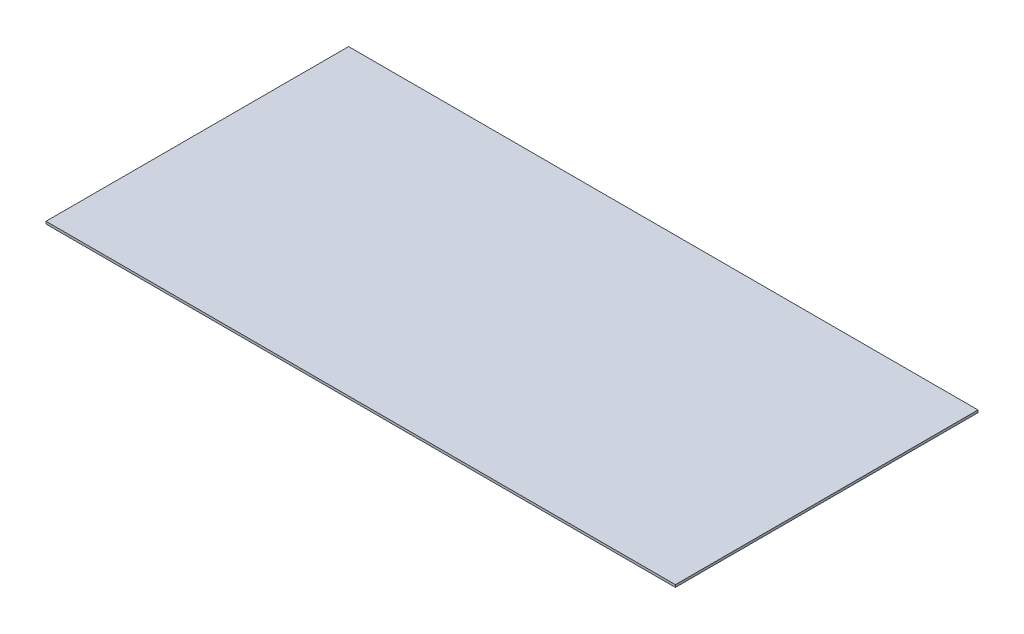
SolidWorks part; units mm, degrees
ref_plane "Front Plane" through (0, 0, 0) normal (0, 0, 1) x (1, 0, 0)
ref_plane "Top Plane" through (0, 0, 0) normal (0, 1, 0) x (1, 0, 0)
ref_plane "Right Plane" through (0, 0, 0) normal (1, 0, 0) x (0, 0, -1)
sketch "Sketch2" plane through (0, 0, 0) normal (0, 1, 0) x (1, 0, 0)
  line L1 (0, 1250) -> (2600, 1250)
  line L2 (0, 1250) -> (0, 0)
  line L3 (0, 0) -> (2600, 0)
  line L4 (2600, 1250) -> (2600, 0)
  dimension "Width" = 1250
  dimension "Length" = 2600
extrude "Extrude1" add sketch "Sketch2" along normal blind 10
sheet metal parameters "Sheet-Metal1" thickness 10 parameters "D1"=10
convert to sheet metal "Convert-Solid1" parameters "D1"=10
sketch "Etch" plane through (0, 0, 0) normal (0, -1, 0) x (1, 0, 0)
  line L0 (2572, -160) -> (2422, -160) construction
  line L1 (2572, -90) -> (2422, -90) construction
  line L2 (2572, -90) -> (2572, -120) construction
  line L3 (2572, -160) -> (2572, -190) construction
  line L4 (2572, -190) -> (2422, -190) construction
  line L5 (2422, -160) -> (2422, -190) construction
  line L6 (2572, -120) -> (2422, -120) construction
  line L7 (2422, -90) -> (2422, -120) construction
  line L8 (2422, -1130) -> (2422, -1160) construction
  line L9 (2572, -1160) -> (2422, -1160) construction
  line L10 (2572, -1130) -> (2572, -1160) construction
  line L11 (2572, -1130) -> (2422, -1130) construction
  line L12 (2572, -1060) -> (2572, -1090) construction
  line L13 (2572, -1060) -> (2422, -1060) construction
  line L14 (2422, -1060) -> (2422, -1090) construction
  line L15 (2572, -1090) -> (2422, -1090) construction
  line L16 (2572, -160) -> (2422, -160)
  line L17 (2572, -90) -> (2422, -90)
  line L18 (2572, -90) -> (2572, -120)
  line L19 (2572, -160) -> (2572, -190)
  line L20 (2572, -190) -> (2422, -190)
  line L21 (2422, -160) -> (2422, -190)
  line L22 (2572, -120) -> (2422, -120)
  line L23 (2422, -90) -> (2422, -120)
  line L24 (2422, -1130) -> (2422, -1160)
  line L25 (2572, -1160) -> (2422, -1160)
  line L26 (2572, -1130) -> (2572, -1160)
  line L27 (2572, -1130) -> (2422, -1130)
  line L28 (2572, -1060) -> (2572, -1090)
  line L29 (2572, -1060) -> (2422, -1060)
  line L30 (2422, -1060) -> (2422, -1090)
  line L31 (2572, -1090) -> (2422, -1090)
sketch "Sketch4" plane through (0, 10, 0) normal (0, 1, 0) x (1, 0, 0)
  circle A0 centre (1184.0011, 660.7352) radius 330.6526
sketch "Sketch5" plane through (0, 10, 0) normal (0, 1, 0) x (1, 0, 0)
  circle A0 centre (1179.6151, 596.7354) radius 277.3059
flat pattern "Flat-Pattern1" [suppressed]
sketch "Bend-Lines1" plane through (0, 0, 0) normal (0, 1, 0) x (1, 0, 0)
sketch3d "Bounding-Box1" [suppressed]
  line L0 (2600, 0, 0) -> (0, 0, 0) construction
  line L1 (2600, 1250, 0) -> (0, 1250, 0) construction
  line L2 (2600, 0, 0) -> (2600, 1250, 0) construction
  line L3 (0, 0, 0) -> (0, 1250, 0) construction
sketch "Etch-1" plane through (0, 0, 0) normal (0, -1, 0) x (1, 0, 0)
  line L16 (2572, -160) -> (2422, -160)
  line L17 (2572, -90) -> (2422, -90)
  line L18 (2572, -90) -> (2572, -120)
  line L19 (2572, -160) -> (2572, -190)
  line L20 (2572, -190) -> (2422, -190)
  line L21 (2422, -160) -> (2422, -190)
  line L22 (2572, -120) -> (2422, -120)
  line L23 (2422, -90) -> (2422, -120)
  line L24 (2422, -1130) -> (2422, -1160)
  line L25 (2572, -1160) -> (2422, -1160)
  line L26 (2572, -1130) -> (2572, -1160)
  line L27 (2572, -1130) -> (2422, -1130)
  line L28 (2572, -1060) -> (2572, -1090)
  line L29 (2572, -1060) -> (2422, -1060)
  line L30 (2422, -1060) -> (2422, -1090)
  line L31 (2572, -1090) -> (2422, -1090)
sketch "Etch-2" plane through (0, 0, 0) normal (0, -1, 0) x (1, 0, 0)
  line L16 (2572, -160) -> (2422, -160)
  line L17 (2572, -90) -> (2422, -90)
  line L18 (2572, -90) -> (2572, -120)
  line L19 (2572, -160) -> (2572, -190)
  line L20 (2572, -190) -> (2422, -190)
  line L21 (2422, -160) -> (2422, -190)
  line L22 (2572, -120) -> (2422, -120)
  line L23 (2422, -90) -> (2422, -120)
  line L24 (2422, -1130) -> (2422, -1160)
  line L25 (2572, -1160) -> (2422, -1160)
  line L26 (2572, -1130) -> (2572, -1160)
  line L27 (2572, -1130) -> (2422, -1130)
  line L28 (2572, -1060) -> (2572, -1090)
  line L29 (2572, -1060) -> (2422, -1060)
  line L30 (2422, -1060) -> (2422, -1090)
  line L31 (2572, -1090) -> (2422, -1090)
sketch "Etch-3" plane through (0, 0, 0) normal (0, -1, 0) x (1, 0, 0)
  line L16 (2572, -160) -> (2422, -160)
  line L17 (2572, -90) -> (2422, -90)
  line L18 (2572, -90) -> (2572, -120)
  line L19 (2572, -160) -> (2572, -190)
  line L20 (2572, -190) -> (2422, -190)
  line L21 (2422, -160) -> (2422, -190)
  line L22 (2572, -120) -> (2422, -120)
  line L23 (2422, -90) -> (2422, -120)
  line L24 (2422, -1130) -> (2422, -1160)
  line L25 (2572, -1160) -> (2422, -1160)
  line L26 (2572, -1130) -> (2572, -1160)
  line L27 (2572, -1130) -> (2422, -1130)
  line L28 (2572, -1060) -> (2572, -1090)
  line L29 (2572, -1060) -> (2422, -1060)
  line L30 (2422, -1060) -> (2422, -1090)
  line L31 (2572, -1090) -> (2422, -1090)
sketch "Etch-4" plane through (0, 0, 0) normal (0, -1, 0) x (1, 0, 0)
  line L16 (2572, -160) -> (2422, -160)
  line L17 (2572, -90) -> (2422, -90)
  line L18 (2572, -90) -> (2572, -120)
  line L19 (2572, -160) -> (2572, -190)
  line L20 (2572, -190) -> (2422, -190)
  line L21 (2422, -160) -> (2422, -190)
  line L22 (2572, -120) -> (2422, -120)
  line L23 (2422, -90) -> (2422, -120)
  line L24 (2422, -1130) -> (2422, -1160)
  line L25 (2572, -1160) -> (2422, -1160)
  line L26 (2572, -1130) -> (2572, -1160)
  line L27 (2572, -1130) -> (2422, -1130)
  line L28 (2572, -1060) -> (2572, -1090)
  line L29 (2572, -1060) -> (2422, -1060)
  line L30 (2422, -1060) -> (2422, -1090)
  line L31 (2572, -1090) -> (2422, -1090)
sketch "Etch-5" plane through (0, 0, 0) normal (0, -1, 0) x (1, 0, 0)
  line L16 (2572, -160) -> (2422, -160)
  line L17 (2572, -90) -> (2422, -90)
  line L18 (2572, -90) -> (2572, -120)
  line L19 (2572, -160) -> (2572, -190)
  line L20 (2572, -190) -> (2422, -190)
  line L21 (2422, -160) -> (2422, -190)
  line L22 (2572, -120) -> (2422, -120)
  line L23 (2422, -90) -> (2422, -120)
  line L24 (2422, -1130) -> (2422, -1160)
  line L25 (2572, -1160) -> (2422, -1160)
  line L26 (2572, -1130) -> (2572, -1160)
  line L27 (2572, -1130) -> (2422, -1130)
  line L28 (2572, -1060) -> (2572, -1090)
  line L29 (2572, -1060) -> (2422, -1060)
  line L30 (2422, -1060) -> (2422, -1090)
  line L31 (2572, -1090) -> (2422, -1090)
sketch "Etch-6" plane through (0, 0, 0) normal (0, -1, 0) x (1, 0, 0)
  line L16 (2572, -160) -> (2422, -160)
  line L17 (2572, -90) -> (2422, -90)
  line L18 (2572, -90) -> (2572, -120)
  line L19 (2572, -160) -> (2572, -190)
  line L20 (2572, -190) -> (2422, -190)
  line L21 (2422, -160) -> (2422, -190)
  line L22 (2572, -120) -> (2422, -120)
  line L23 (2422, -90) -> (2422, -120)
  line L24 (2422, -1130) -> (2422, -1160)
  line L25 (2572, -1160) -> (2422, -1160)
  line L26 (2572, -1130) -> (2572, -1160)
  line L27 (2572, -1130) -> (2422, -1130)
  line L28 (2572, -1060) -> (2572, -1090)
  line L29 (2572, -1060) -> (2422, -1060)
  line L30 (2422, -1060) -> (2422, -1090)
  line L31 (2572, -1090) -> (2422, -1090)
sketch "Etch-7" plane through (0, 0, 0) normal (0, -1, 0) x (1, 0, 0)
  line L16 (2572, -160) -> (2422, -160)
  line L17 (2572, -90) -> (2422, -90)
  line L18 (2572, -90) -> (2572, -120)
  line L19 (2572, -160) -> (2572, -190)
  line L20 (2572, -190) -> (2422, -190)
  line L21 (2422, -160) -> (2422, -190)
  line L22 (2572, -120) -> (2422, -120)
  line L23 (2422, -90) -> (2422, -120)
  line L24 (2422, -1130) -> (2422, -1160)
  line L25 (2572, -1160) -> (2422, -1160)
  line L26 (2572, -1130) -> (2572, -1160)
  line L27 (2572, -1130) -> (2422, -1130)
  line L28 (2572, -1060) -> (2572, -1090)
  line L29 (2572, -1060) -> (2422, -1060)
  line L30 (2422, -1060) -> (2422, -1090)
  line L31 (2572, -1090) -> (2422, -1090)
sketch "Etch-8" plane through (0, 0, 0) normal (0, -1, 0) x (1, 0, 0)
  line L16 (2572, -160) -> (2422, -160)
  line L17 (2572, -90) -> (2422, -90)
  line L18 (2572, -90) -> (2572, -120)
  line L19 (2572, -160) -> (2572, -190)
  line L20 (2572, -190) -> (2422, -190)
  line L21 (2422, -160) -> (2422, -190)
  line L22 (2572, -120) -> (2422, -120)
  line L23 (2422, -90) -> (2422, -120)
  line L24 (2422, -1130) -> (2422, -1160)
  line L25 (2572, -1160) -> (2422, -1160)
  line L26 (2572, -1130) -> (2572, -1160)
  line L27 (2572, -1130) -> (2422, -1130)
  line L28 (2572, -1060) -> (2572, -1090)
  line L29 (2572, -1060) -> (2422, -1060)
  line L30 (2422, -1060) -> (2422, -1090)
  line L31 (2572, -1090) -> (2422, -1090)
sketch "Etch-9" plane through (0, 0, 0) normal (0, -1, 0) x (1, 0, 0)
  line L16 (2572, -160) -> (2422, -160)
  line L17 (2572, -90) -> (2422, -90)
  line L18 (2572, -90) -> (2572, -120)
  line L19 (2572, -160) -> (2572, -190)
  line L20 (2572, -190) -> (2422, -190)
  line L21 (2422, -160) -> (2422, -190)
  line L22 (2572, -120) -> (2422, -120)
  line L23 (2422, -90) -> (2422, -120)
  line L24 (2422, -1130) -> (2422, -1160)
  line L25 (2572, -1160) -> (2422, -1160)
  line L26 (2572, -1130) -> (2572, -1160)
  line L27 (2572, -1130) -> (2422, -1130)
  line L28 (2572, -1060) -> (2572, -1090)
  line L29 (2572, -1060) -> (2422, -1060)
  line L30 (2422, -1060) -> (2422, -1090)
  line L31 (2572, -1090) -> (2422, -1090)
sketch "Etch-10" plane through (0, 0, 0) normal (0, -1, 0) x (1, 0, 0)
  line L16 (2572, -160) -> (2422, -160)
  line L17 (2572, -90) -> (2422, -90)
  line L18 (2572, -90) -> (2572, -120)
  line L19 (2572, -160) -> (2572, -190)
  line L20 (2572, -190) -> (2422, -190)
  line L21 (2422, -160) -> (2422, -190)
  line L22 (2572, -120) -> (2422, -120)
  line L23 (2422, -90) -> (2422, -120)
  line L24 (2422, -1130) -> (2422, -1160)
  line L25 (2572, -1160) -> (2422, -1160)
  line L26 (2572, -1130) -> (2572, -1160)
  line L27 (2572, -1130) -> (2422, -1130)
  line L28 (2572, -1060) -> (2572, -1090)
  line L29 (2572, -1060) -> (2422, -1060)
  line L30 (2422, -1060) -> (2422, -1090)
  line L31 (2572, -1090) -> (2422, -1090)
sketch "Etch-11" plane through (0, 0, 0) normal (0, -1, 0) x (1, 0, 0)
  line L16 (2572, -160) -> (2422, -160)
  line L17 (2572, -90) -> (2422, -90)
  line L18 (2572, -90) -> (2572, -120)
  line L19 (2572, -160) -> (2572, -190)
  line L20 (2572, -190) -> (2422, -190)
  line L21 (2422, -160) -> (2422, -190)
  line L22 (2572, -120) -> (2422, -120)
  line L23 (2422, -90) -> (2422, -120)
  line L24 (2422, -1130) -> (2422, -1160)
  line L25 (2572, -1160) -> (2422, -1160)
  line L26 (2572, -1130) -> (2572, -1160)
  line L27 (2572, -1130) -> (2422, -1130)
  line L28 (2572, -1060) -> (2572, -1090)
  line L29 (2572, -1060) -> (2422, -1060)
  line L30 (2422, -1060) -> (2422, -1090)
  line L31 (2572, -1090) -> (2422, -1090)
sketch "Etch-12" plane through (0, 0, 0) normal (0, -1, 0) x (1, 0, 0)
  line L16 (2572, -160) -> (2422, -160)
  line L17 (2572, -90) -> (2422, -90)
  line L18 (2572, -90) -> (2572, -120)
  line L19 (2572, -160) -> (2572, -190)
  line L20 (2572, -190) -> (2422, -190)
  line L21 (2422, -160) -> (2422, -190)
  line L22 (2572, -120) -> (2422, -120)
  line L23 (2422, -90) -> (2422, -120)
  line L24 (2422, -1130) -> (2422, -1160)
  line L25 (2572, -1160) -> (2422, -1160)
  line L26 (2572, -1130) -> (2572, -1160)
  line L27 (2572, -1130) -> (2422, -1130)
  line L28 (2572, -1060) -> (2572, -1090)
  line L29 (2572, -1060) -> (2422, -1060)
  line L30 (2422, -1060) -> (2422, -1090)
  line L31 (2572, -1090) -> (2422, -1090)
sketch "Etch-13" plane through (0, 0, 0) normal (0, -1, 0) x (1, 0, 0)
  line L16 (2572, -160) -> (2422, -160)
  line L17 (2572, -90) -> (2422, -90)
  line L18 (2572, -90) -> (2572, -120)
  line L19 (2572, -160) -> (2572, -190)
  line L20 (2572, -190) -> (2422, -190)
  line L21 (2422, -160) -> (2422, -190)
  line L22 (2572, -120) -> (2422, -120)
  line L23 (2422, -90) -> (2422, -120)
  line L24 (2422, -1130) -> (2422, -1160)
  line L25 (2572, -1160) -> (2422, -1160)
  line L26 (2572, -1130) -> (2572, -1160)
  line L27 (2572, -1130) -> (2422, -1130)
  line L28 (2572, -1060) -> (2572, -1090)
  line L29 (2572, -1060) -> (2422, -1060)
  line L30 (2422, -1060) -> (2422, -1090)
  line L31 (2572, -1090) -> (2422, -1090)
sketch "Etch-14" plane through (0, 0, 0) normal (0, -1, 0) x (1, 0, 0)
  line L16 (2572, -160) -> (2422, -160)
  line L17 (2572, -90) -> (2422, -90)
  line L18 (2572, -90) -> (2572, -120)
  line L19 (2572, -160) -> (2572, -190)
  line L20 (2572, -190) -> (2422, -190)
  line L21 (2422, -160) -> (2422, -190)
  line L22 (2572, -120) -> (2422, -120)
  line L23 (2422, -90) -> (2422, -120)
  line L24 (2422, -1130) -> (2422, -1160)
  line L25 (2572, -1160) -> (2422, -1160)
  line L26 (2572, -1130) -> (2572, -1160)
  line L27 (2572, -1130) -> (2422, -1130)
  line L28 (2572, -1060) -> (2572, -1090)
  line L29 (2572, -1060) -> (2422, -1060)
  line L30 (2422, -1060) -> (2422, -1090)
  line L31 (2572, -1090) -> (2422, -1090)
sketch "Etch-15" plane through (0, 0, 0) normal (0, -1, 0) x (1, 0, 0)
  line L16 (2572, -160) -> (2422, -160)
  line L17 (2572, -90) -> (2422, -90)
  line L18 (2572, -90) -> (2572, -120)
  line L19 (2572, -160) -> (2572, -190)
  line L20 (2572, -190) -> (2422, -190)
  line L21 (2422, -160) -> (2422, -190)
  line L22 (2572, -120) -> (2422, -120)
  line L23 (2422, -90) -> (2422, -120)
  line L24 (2422, -1130) -> (2422, -1160)
  line L25 (2572, -1160) -> (2422, -1160)
  line L26 (2572, -1130) -> (2572, -1160)
  line L27 (2572, -1130) -> (2422, -1130)
  line L28 (2572, -1060) -> (2572, -1090)
  line L29 (2572, -1060) -> (2422, -1060)
  line L30 (2422, -1060) -> (2422, -1090)
  line L31 (2572, -1090) -> (2422, -1090)
sketch "Etch-16" plane through (0, 0, 0) normal (0, -1, 0) x (1, 0, 0)
  line L16 (2572, -160) -> (2422, -160)
  line L17 (2572, -90) -> (2422, -90)
  line L18 (2572, -90) -> (2572, -120)
  line L19 (2572, -160) -> (2572, -190)
  line L20 (2572, -190) -> (2422, -190)
  line L21 (2422, -160) -> (2422, -190)
  line L22 (2572, -120) -> (2422, -120)
  line L23 (2422, -90) -> (2422, -120)
  line L24 (2422, -1130) -> (2422, -1160)
  line L25 (2572, -1160) -> (2422, -1160)
  line L26 (2572, -1130) -> (2572, -1160)
  line L27 (2572, -1130) -> (2422, -1130)
  line L28 (2572, -1060) -> (2572, -1090)
  line L29 (2572, -1060) -> (2422, -1060)
  line L30 (2422, -1060) -> (2422, -1090)
  line L31 (2572, -1090) -> (2422, -1090)
sketch "Etch-17" plane through (0, 0, 0) normal (0, -1, 0) x (1, 0, 0)
  line L16 (2572, -160) -> (2422, -160)
  line L17 (2572, -90) -> (2422, -90)
  line L18 (2572, -90) -> (2572, -120)
  line L19 (2572, -160) -> (2572, -190)
  line L20 (2572, -190) -> (2422, -190)
  line L21 (2422, -160) -> (2422, -190)
  line L22 (2572, -120) -> (2422, -120)
  line L23 (2422, -90) -> (2422, -120)
  line L24 (2422, -1130) -> (2422, -1160)
  line L25 (2572, -1160) -> (2422, -1160)
  line L26 (2572, -1130) -> (2572, -1160)
  line L27 (2572, -1130) -> (2422, -1130)
  line L28 (2572, -1060) -> (2572, -1090)
  line L29 (2572, -1060) -> (2422, -1060)
  line L30 (2422, -1060) -> (2422, -1090)
  line L31 (2572, -1090) -> (2422, -1090)
sketch "Etch-18" plane through (0, 0, 0) normal (0, -1, 0) x (1, 0, 0)
  line L16 (2572, -160) -> (2422, -160)
  line L17 (2572, -90) -> (2422, -90)
  line L18 (2572, -90) -> (2572, -120)
  line L19 (2572, -160) -> (2572, -190)
  line L20 (2572, -190) -> (2422, -190)
  line L21 (2422, -160) -> (2422, -190)
  line L22 (2572, -120) -> (2422, -120)
  line L23 (2422, -90) -> (2422, -120)
  line L24 (2422, -1130) -> (2422, -1160)
  line L25 (2572, -1160) -> (2422, -1160)
  line L26 (2572, -1130) -> (2572, -1160)
  line L27 (2572, -1130) -> (2422, -1130)
  line L28 (2572, -1060) -> (2572, -1090)
  line L29 (2572, -1060) -> (2422, -1060)
  line L30 (2422, -1060) -> (2422, -1090)
  line L31 (2572, -1090) -> (2422, -1090)
sketch "Etch-19" plane through (0, 0, 0) normal (0, -1, 0) x (1, 0, 0)
  line L16 (2572, -160) -> (2422, -160)
  line L17 (2572, -90) -> (2422, -90)
  line L18 (2572, -90) -> (2572, -120)
  line L19 (2572, -160) -> (2572, -190)
  line L20 (2572, -190) -> (2422, -190)
  line L21 (2422, -160) -> (2422, -190)
  line L22 (2572, -120) -> (2422, -120)
  line L23 (2422, -90) -> (2422, -120)
  line L24 (2422, -1130) -> (2422, -1160)
  line L25 (2572, -1160) -> (2422, -1160)
  line L26 (2572, -1130) -> (2572, -1160)
  line L27 (2572, -1130) -> (2422, -1130)
  line L28 (2572, -1060) -> (2572, -1090)
  line L29 (2572, -1060) -> (2422, -1060)
  line L30 (2422, -1060) -> (2422, -1090)
  line L31 (2572, -1090) -> (2422, -1090)
